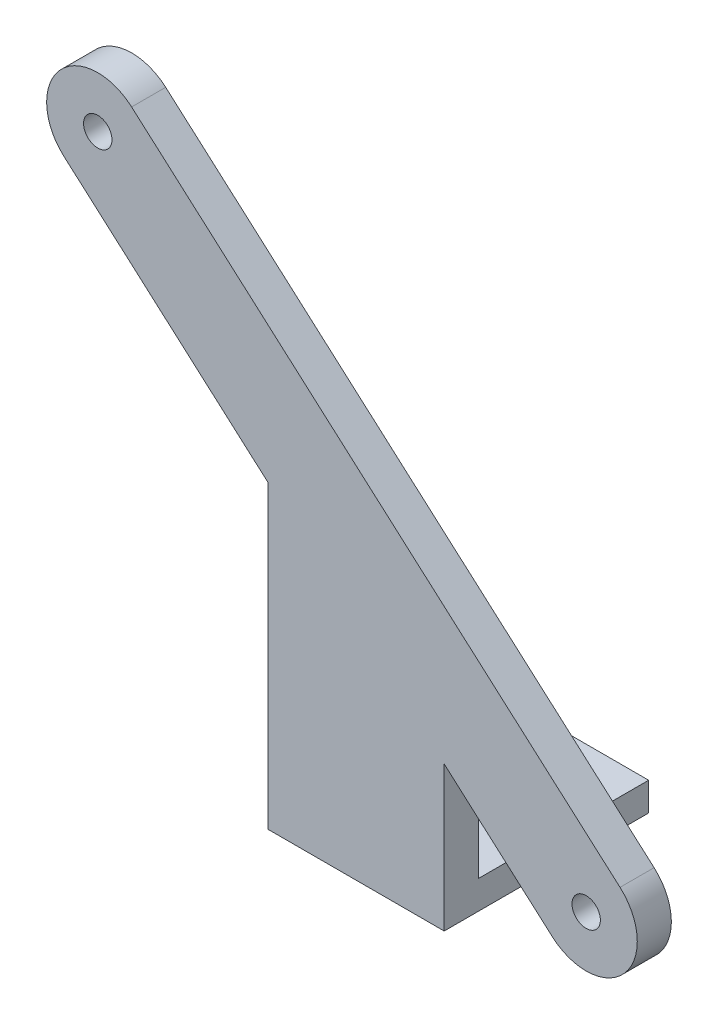
SolidWorks part; units mm, degrees
ref_plane "Front Plane" through (0, 0, 0) normal (0, 0, 1) x (1, 0, 0)
ref_plane "Top Plane" through (0, 0, 0) normal (0, 1, 0) x (1, 0, 0)
ref_plane "Right Plane" through (0, 0, 0) normal (1, 0, 0) x (0, 0, -1)
sketch "Sketch1" plane through (0, 0, 0) normal (0, 0, 1) x (1, 0, 0)
  line L0 (-21.5, 45.7) -> (21.5, 7.7) construction
  line L1 (-21.5, 45.7) -> (21.5, 7.7) construction
  line L2 (-18.5201, 49.072) -> (24.4799, 11.072)
  line L3 (-24.4799, 42.328) -> (18.5201, 4.328)
  line L4 (-9, 28.6481) -> (-9, 0)
  line L5 (-9, 0) -> (9, 0)
  line L6 (0, 0) -> (0, 26.7) construction
  line L7 (9, 0) -> (9, 12.7411)
  circle A0 centre (-21.5, 45.7) radius 1.25
  circle A1 centre (21.5, 7.7) radius 1.25
  arc A2 (-18.5201, 49.072) -> (-24.4799, 42.328) centre (-21.5, 45.7) ccw
  arc A3 (18.5201, 4.328) -> (24.4799, 11.072) centre (21.5, 7.7) ccw
  point P4 (0, 26.7)
  dimension "D3" = 2.5
  dimension "D4" = 4.5
  dimension "D1" = 43
  dimension "D2" = 38
  dimension "D5" = 7.7
  dimension "D6" = 18
extrude "Boss-Extrude1" add sketch "Sketch1" along normal blind 3 contours L3 A3 L2 A2 A0 A1 | A3 L3 L4 L5 region at (0, 26.7, 0) region at (-1.153, 10.8568, 0)
sketch "Sketch2" plane through (0, 0, 0) normal (0, 0, -1) x (-1, 0, 0)
  line L0 (9, 28.6481) -> (9, 0) construction
  line L1 (-9, 0) -> (9, 0)
  line L2 (-9, 0) -> (-9, 2.5)
  line L3 (-9, 2.5) -> (9, 2.5)
  line L4 (9, 0) -> (9, 2.5)
  line L5 (0, 2.5) -> (0, 0) construction
  line L6 (-9, 1.25) -> (9, 1.25) construction
  point P144 (0, 1.25)
  dimension "D1" = 2.5
extrude "Boss-Extrude2" add sketch "Sketch2" along normal blind 15
other "Move Face1" flip direction yes face at (-9, 10.3827, -4) offset 2.5 parameters "D1"=2.5
hole_wizard "M3 Clearance Hole1" positions "Sketch3" profile "Sketch4" hole size "M3" standard "ANSI Metric" end condition up to next
sketch "Sketch3" plane through (0, 2.5, 0) normal (0, 1, 0) x (1, 0, 0)
  line L0 (4.7855, 11.0355) -> (-2.2855, 3.9645) construction
  line L3 (-6.5, 7.5) -> (1.25, 7.5) construction
  line L4 (-6.5, 15) -> (-6.5, 0) construction
  line L5 (1.25, 7.5) -> (1.25, 15) construction
  line L6 (-6.5, 15) -> (9, 15) construction
  point P0 (-2.2855, 3.9645)
  point P2 (4.7855, 11.0355)
  dimension "D1" = 45
  dimension "D2" = 10
sketch "Sketch4" plane through (-2.2855, 2.5, -3.9645) normal (1, 0, 0) x (0, 0, 1)
  line L0 (0, 0) -> (0, 2.5)
  line L1 (0, 2.5) -> (1.7, 2.5)
  line L2 (1.7, 2.5) -> (1.7, 0)
  line L5 (1.7, 0) -> (0, 0)
  line L11 (0, -6.35) -> (0, 107.95) construction
  dimension "Thru Hole Dia." = 3.4
  dimension "Thru Hole Depth" = 2.5
